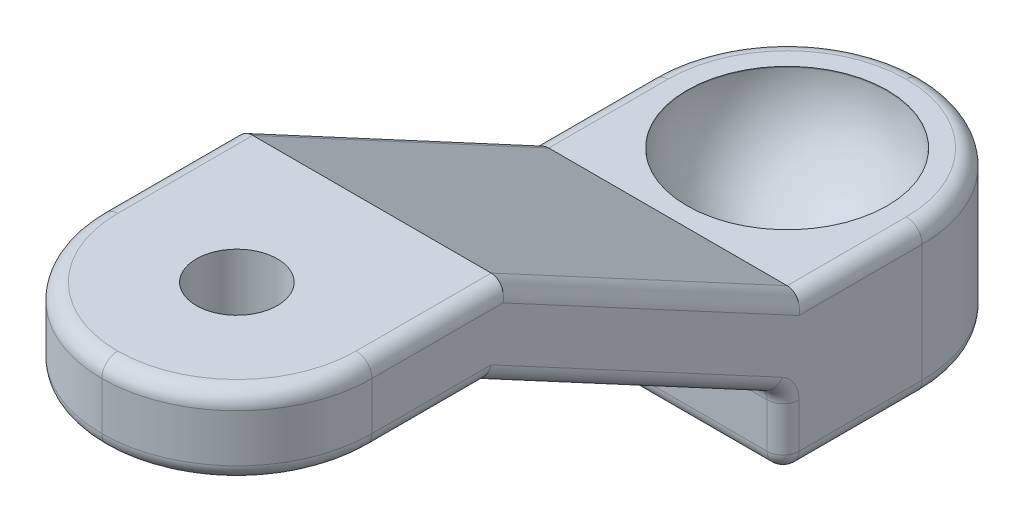
SolidWorks part; units mm, degrees
ref_plane "Front Plane" through (0, 0, 0) normal (0, 0, 1) x (1, 0, 0)
ref_plane "Top Plane" through (0, 0, 0) normal (0, 1, 0) x (1, 0, 0)
ref_plane "Right Plane" through (0, 0, 0) normal (1, 0, 0) x (0, 0, -1)
sketch "ProfileSketch1" plane through (0, 0, 0) normal (1, 0, 0) x (0, 0, -1)
  line L0 (0, 0) -> (34, 0)
  line L1 (34, 0) -> (71.2531, -20)
  line L2 (71.2531, -20) -> (103.2531, -20)
  line L3 (17, 0) -> (17, 2.8642) construction
  line L4 (87.2531, -20) -> (87.2531, 2.8642) construction
  dimension "D1" = 34
  dimension "D2" = 20
  dimension "D4" = 32
  dimension "D3" = 70.2531
extrude "ProfileExtrude-Thin1" add sketch "ProfileSketch1" along normal blind 34 thin thin type one direction wall 10
sketch "DomePadExtensionSketch1" plane through (0, -30, 0) normal (0, -1, 0) x (1, 0, 0)
  line L1 (0, -68.7385) -> (34, -68.7385)
  line L2 (0, -68.7385) -> (0, -103.2531)
  line L3 (0, -103.2531) -> (34, -103.2531)
  line L4 (34, -68.7385) -> (34, -103.2531)
extrude "DomePadExtensionBoss-Extrude1" add sketch "DomePadExtensionSketch1" along normal blind 8.8
fillet "Fillet1" radius 17 1 edges at (34, -5, 0)
fillet "Fillet2" radius 17 1 edges at (0, -5, 0)
sketch "FlangeNutHoleSketch4" plane through (0, 0, 0) normal (0, 1, 0) x (1, 0, 0)
  line L0 (0, 17) -> (0, 34) construction
  line L1 (34, 34) -> (0, 34) construction
  circle A0 centre (17, 17) radius 5.1
  dimension "D1" = 17
  dimension "D3" = 10.2
  dimension "D2" = 17
extrude "FlangeNutHoleCut-Extrude5" cut sketch "FlangeNutHoleSketch4" against normal through all
sketch "DomeIndentSketch6" plane through (0, -20, 0) normal (0, 1, 0) x (1, 0, 0)
  line L4 (0, 71.2531) -> (0, 103.2531) construction
  line L5 (34, 103.2531) -> (0, 103.2531) construction
  circle A0 centre (17, 86.2531) radius 12.6
  dimension "D2" = 17
  dimension "D1" = 25.2
  dimension "D3" = 17
extrude "DomeIndentCut-Extrude8" cut sketch "DomeIndentSketch6" against normal blind 0.1
dome "Dome2" faces to dome 1 distance 12.5 reverse direction yes elliptical dome no face at (17, -20.1, -73.6531) parameters "D1"=12.5
fillet "Fillet3" radius 17 1 edges at (34, -29.4, -103.2531)
fillet "Fillet4" radius 17 1 edges at (0, -29.4, -103.2531)
sketch "FlangeNutHolesSketch2" plane through (0, -10, 0) normal (0, -1, 0) x (1, 0, 0)
  line L0 (32, -31.2943) -> (32, -17) construction
  line L1 (34, -31.4854) -> (0, -31.4854) construction
  circle A0 centre (11.3431, -11.3431) radius 2
  circle A1 centre (22.6569, -11.3431) radius 2
  circle A2 centre (22.6569, -22.6569) radius 2
  circle A3 centre (11.3431, -22.6569) radius 2
  point P16 (17, -17)
  dimension "D2" = 4
  dimension "D1" = 8
  dimension "D4" = 8
  dimension "D3" = 4
fillet "BottomBoundaryFillet5" radius 2 14 edges at (0, -20, -50.112) (34, -20, -50.112) (34, -10, -24.2427) (29.0208, -10, -4.9792) (4.9792, -10, -4.9792) (0, -10, -24.2427) (34, -38.8, -77.4958) (29.0208, -38.8, -98.2739) (4.9792, -38.8, -98.2739) (34, -34.4, -68.7385) (17, -38.8, -68.7385) (0, -34.4, -68.7385) (17, -30, -68.7385) (0, -38.8, -77.4958)
extrude "FlangeNutHolesCut-Extrude1" cut sketch "FlangeNutHolesSketch2" against normal blind 4
fillet "Fillet6" radius 2 10 edges at (34, -10, -52.6266) (34, 0, -25.5) (29.0208, 0, -4.9792) (4.9792, 0, -4.9792) (0, 0, -25.5) (0, -10, -52.6266) (0, -20, -78.7531) (4.9792, -20, -98.2739) (34, -20, -78.7531) (29.0208, -20, -98.2739)
equation "\"D1@ProfileSketch1\"=\"BedSupportLeadScrewPadSize\""
equation "\"StandardWallThickness\"= 3mm"
equation "\"BedToBuildPlateStandoffPadSize\"= 10mm"
equation "\"BuildPlateStandoffHolesDistanceFromLeftOrRight\"= 7mm"
equation "\"BuildPlateStandoffHolesDistanceFromFrontOrBack\"= 41mm"
equation "\"DistanceFromBuildPlateSideToStepperHole\"= ( \"DistanceBetweenLeftToRightStepperHoles\" - \"BuildPlateWidth\" ) / 2'Equals 55.825"
equation "\"DistanceBetweenLeftToRightStepperHoles\"= \"FrontBackRailLength\" - \"StepperMountingHoleOffsetFromLeftOrRightSide\" * 2 - \"StepperMountingHoleDistance\"'Equals 461.65"
equation "\"FrontBackRailLength\"= 510mm"
equation "\"StepperMountingHoleOffsetFromLeftOrRightSide\"= \"StepperMountingHoleOffsetFromItsSide\" + \"RailThickness\""
equation "\"StepperMountingHoleDistance\"= 31mm'Spec"
equation "\"StepperMountingHoleOffsetFromItsSide\"= 5.5mm'Spec"
equation "\"RailThickness\"= .125in'Spec"
equation "\"LeadScrewNutPadSize\"= \"LeadScrewNutMountingHoleFlangeDiameter\" + 2mm'Equals 24"
equation "\"LeadScrewNutInnerShaftFlangeDiameter\"= 10.2mm'Spec"
equation "\"LeadScrewNutMountHoleDiameter\"= \"M3HeatInsertHoleDiameter\""
equation "\"LeadScrewNutMountingHoleFlangeDiameter\"= 22mm'Spec"
equation "\"LeadScrewNutMountingHoleDistance\"= 16mm'Spec"
equation "\"M3HeatInsertHoleDiameter\"= 4mm'Spec"
equation "\"D1@Fillet1\"=\"BedSupportLeadScrewPadSize\"/2"
equation "\"D1@Fillet2\"=\"BedSupportLeadScrewPadSize\"/2"
equation "\"D1@FlangeNutHoleSketch4\"=\"BedSupportLeadScrewPadSize\"  / 2"
equation "\"D2@FlangeNutHoleSketch4\"=\"BedSupportLeadScrewPadSize\" / 2"
equation "\"D3@FlangeNutHoleSketch4\" = \"LeadScrewNutInnerShaftFlangeDiameter\""
equation "\"D2@DomeIndentSketch6\" = \"BedSupportLeadScrewPadSize\" / 2"
equation "\"D3@DomeIndentSketch6\" = \"BedSupportLeadScrewPadSize\" / 2"
equation "\"BedSpringHoleSize\"= 3mm"
equation "\"BuildPlateWidth\"= 350mm'Spec"
equation "\"BuildPlateLength\"= 350mm'Spec"
equation "\"BuildPlateBoreDiameter\"= 5mm'Spec"
equation "\"BuildPlateBoreDepth\"= 3mm'Spec"
equation "\"BuildPlateDepth\"= 8mm'Spec"
equation "\"BuildPlateFlankingHoles\"= 38mm"
equation "\"BuildPlateStandoffHolesDistanceFromFront\"= 7mm"
equation "\"BedSupportLeadScrewPadSize\"= \"LeadScrewNutPadSize\" + 10mm"
equation "\"D1@ProfileExtrude-Thin1\"=\"BedSupportLeadScrewPadSize\""
equation "\"BuildPlateBallDiameter\"= 12mm"
equation "\"BedSupportBuildPlatePadSize\"= \"BuildPlateBallDiameter\" + 20mm"
equation "\"D4@ProfileSketch1\"=\"BedSupportBuildPlatePadSize\""
equation "\"D3@ProfileSketch1\"=\"HypotonusOfStepperAndBuildPlateHoles\"+3mm"
equation "\"D1@Fillet3\"=\"BedSupportLeadScrewPadSize\"/2"
equation "\"D1@Fillet4\"=\"BedSupportLeadScrewPadSize\"/2"
equation "\"HypotonusOfStepperAndBuildPlateHoles\"= sqr ( ( \"DistanceFromBuildPlateSideToStepperHole\" + \"BuildPlateStandoffHolesDistanceFromLeftOrRight\" ) ^ 2 + ( \"BuildPlateStandoffHolesDistanceFromFrontOrBack\" - \"BedSupportLeadScrewPadSize\" / 2 ) ^ 2 )"
equation "\"D1@FlangeNutHolesCut-Extrude1\" = \"M3HeatInsertHoleDiameter\""
equation "\"D1@FlangeNutHolesSketch2\"=\"LeadScrewNutMountingHoleDistance\"/2"
equation "\"D2@FlangeNutHolesSketch2\"=\"M3HeatInsertHoleDiameter\""
equation "\"D4@FlangeNutHolesSketch2\"=\"LeadScrewNutMountingHoleDistance\"/2"
equation "\"BallNutDiameter\"= 25mm + .2mm'Added .2mm for filament expansion"
equation "\"D1@DomeIndentSketch6\"=\"BallNutDiameter\""
equation "\"D1@DomePadExtensionBoss-Extrude1\" = \"BedSupportBuildPlatePadSize\" - \"BallNutDiameter\" + 2mm"
